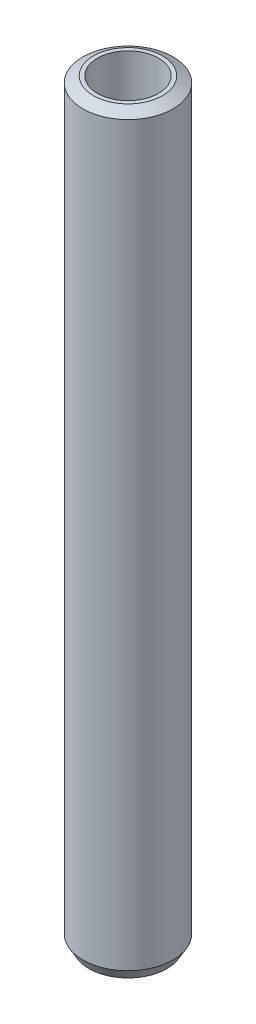
SolidWorks part; units mm, degrees
ref_plane "Front Plane" through (0, 0, 0) normal (0, 0, 1) x (1, 0, 0)
ref_plane "Top Plane" through (0, 0, 0) normal (0, 1, 0) x (1, 0, 0)
ref_plane "Right Plane" through (0, 0, 0) normal (1, 0, 0) x (0, 0, -1)
sketch "Sketch1" plane through (0, 0, 0) normal (0, 1, 0) x (1, 0, 0)
  circle A0 centre (0, 0) radius 20
  dimension "SHAFT_OD" = 40
extrude "Boss-Extrude1" add sketch "Sketch1" along normal blind 334.3027
sketch "Sketch2" plane through (0, 0, 0) normal (0, 1, 0) x (1, 0, 0)
  circle A0 centre (0, 0) radius 13.5544
  dimension "BORE_D" = 27.1088
extrude "Cut-Extrude1" cut sketch "Sketch2" along normal through all
chamfer "Chamfer1" distance 2.7097 angle 60 2 edges at (0, 334.3027, 20) (0, 0, 20) first distance on face at (0, 334.3027, 20) first distance on face at (0, 0, 13.5544)
